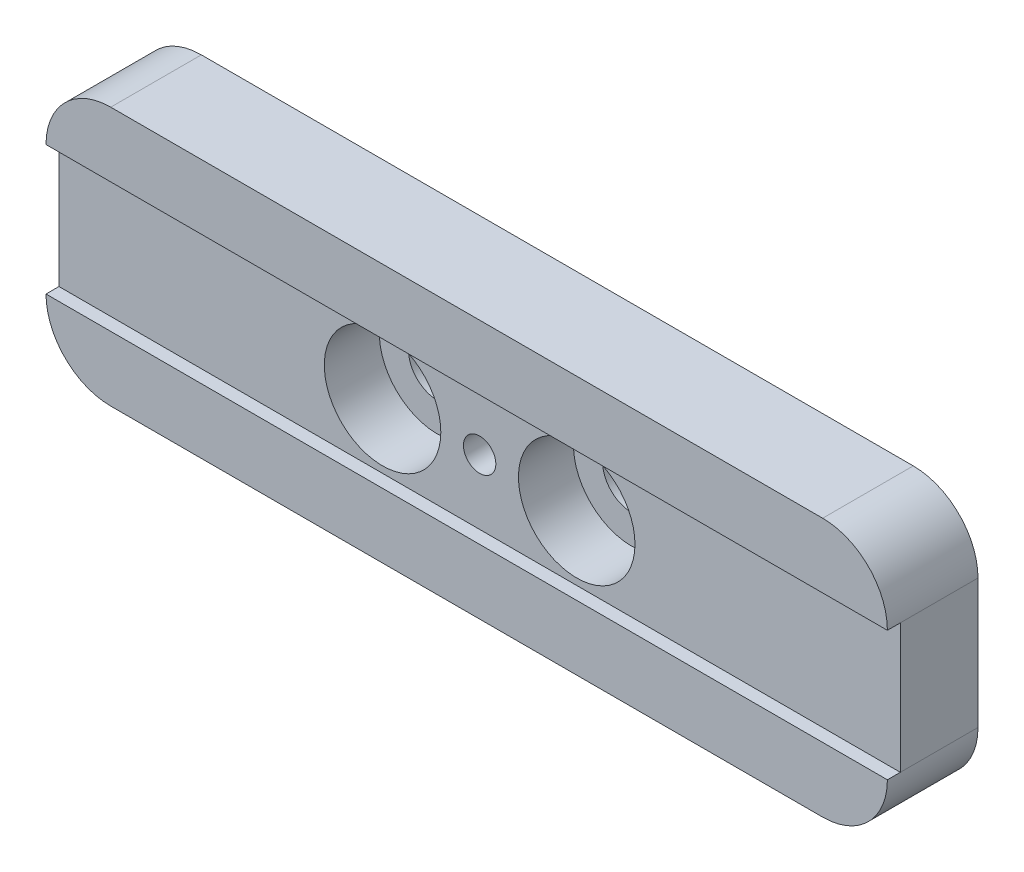
SolidWorks part; units mm, degrees
ref_plane "前视基准面" through (0, 0, 0) normal (0, 0, 1) x (1, 0, 0)
ref_plane "上视基准面" through (0, 0, 0) normal (0, 1, 0) x (1, 0, 0)
ref_plane "右视基准面" through (0, 0, 0) normal (1, 0, 0) x (0, 0, -1)
sketch "草图1" plane through (0, 0, 0) normal (0, 0, 1) x (1, 0, 0)
  line L1 (-65, 40) -> (65, 40)
  line L2 (-65, 40) -> (-65, 0)
  line L3 (-65, 0) -> (65, 0)
  line L4 (65, 40) -> (65, 0)
  dimension "D1" = 130
  dimension "D2" = 40
extrude "凸台-拉伸1" add sketch "草图1" along normal blind 14
hole_wizard "M6 螺纹孔1" positions "草图4" profile "草图5" tap size "M6" standard "GB" end condition through all
sketch "草图4" plane through (0, 0, 14) normal (0, 0, 1) x (1, 0, 0)
  line L0 (65, 0) -> (65, 40) construction
  line L1 (-65, 0) -> (65, 0) construction
  point P0 (0, 20)
  dimension "D1" = 65
  dimension "D2" = 20
sketch "草图5" plane through (0, 20, 14) normal (1, 0, 0) x (0, -1, 0)
  line L0 (0, 0) -> (0, 14)
  line L1 (0, 14) -> (2.5, 14)
  line L2 (2.5, 14) -> (2.5, 0)
  line L5 (2.5, 0) -> (0, 0)
  line L11 (0, -6.35) -> (0, 107.95) construction
  dimension "通孔螺纹孔钻头直径" = 5
  dimension "通孔螺纹孔钻头深度" = 14
cosmetic thread "孔螺蚊线1" parameters "D2"=6
sketch "草图8" plane through (0, 0, 14) normal (0, 0, 1) x (1, 0, 0)
  line L0 (65, 0) -> (65, 40) construction
  line L1 (-65, 10) -> (65, 10)
  line L2 (-65, 10) -> (-65, 30)
  line L3 (-65, 30) -> (65, 30)
  line L4 (65, 10) -> (65, 30)
  line L5 (-65, 10) -> (65, 30) construction
  line L6 (-65, 30) -> (65, 10) construction
  point P0 (0, 20)
  dimension "D1" = 20
extrude "切除-拉伸1" cut sketch "草图8" against normal blind 2
hole_wizard "M8 六角头螺栓的柱形沉头孔1" positions "草图10" profile "草图9" counterbore size "M8" standard "GB" end condition through all
sketch "草图10" plane through (0, 0, 12) normal (0, 0, 1) x (1, 0, 0)
  line L0 (-65, 0) -> (65, 0) construction
  point P0 (-15, 20)
  point P1 (15, 20)
  dimension "D1" = 20
  dimension "D2" = 20
  dimension "D3" = 30
  dimension "D4" = 15
sketch "草图9" plane through (-15, 20, 12) normal (1, 0, 0) x (0, -1, 0)
  line L0 (0, 0) -> (0, 12)
  line L1 (0, 12) -> (4.5, 12)
  line L3 (4.5, 12) -> (4.5, 8.5)
  line L4 (4.5, 8.5) -> (9, 8.5)
  line L5 (9, 8.5) -> (9, 0)
  line L7 (9, 0) -> (0, 0)
  line L11 (0, -6.35) -> (0, 107.95) construction
  dimension "通孔孔直径" = 9
  dimension "通孔孔深度" = 12
  dimension "柱形沉头孔直径" = 18
  dimension "柱形沉头孔深度" = 8.5
fillet "圆角1" radius 10 4 edges at (65, 0, 7) (65, 40, 7) (-65, 0, 7) (-65, 40, 7)
